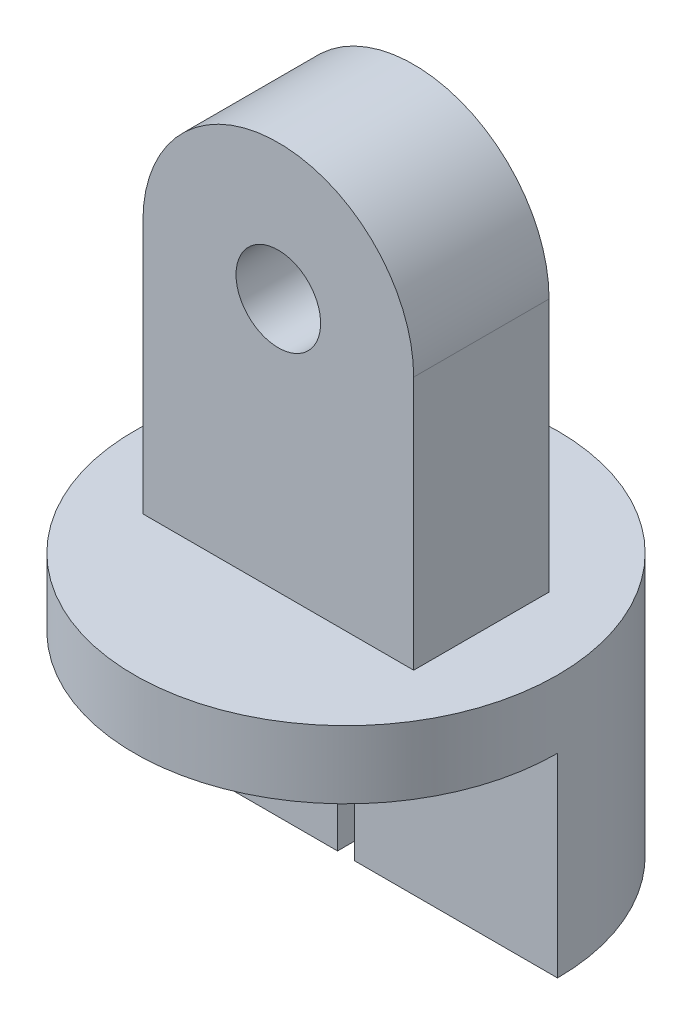
SolidWorks part; units mm, degrees
ref_plane "Front Plane" through (0, 0, 0) normal (0, 0, 1) x (1, 0, 0)
ref_plane "Top Plane" through (0, 0, 0) normal (0, 1, 0) x (1, 0, 0)
ref_plane "Right Plane" through (0, 0, 0) normal (1, 0, 0) x (0, 0, -1)
sketch "Sketch3" plane through (0, 0, 0) normal (0, 0, 1) x (1, 0, 0)
  line L0 (8, 0) -> (-8, 0) construction
  line L1 (8, 0) -> (8, -15)
  line L2 (-8, 0) -> (-8, -15)
  line L3 (8, -15) -> (-8, -15)
  arc A0 (8, 0) -> (-8, 0) centre (0, 0) ccw
  dimension "D1" = 16
  dimension "D2" = 15
extrude "Boss-Extrude2" add sketch "Sketch3" along normal mid plane 8
sketch "Sketch4" plane through (0, 0, -4) normal (0, 0, -1) x (-1, 0, 0)
  circle A0 centre (0, 0) radius 2.5
  dimension "D1" = 5
extrude "Cut-Extrude1" cut sketch "Sketch4" against normal through all
sketch "Sketch6" plane through (0, -15, 0) normal (0, -1, 0) x (1, 0, 0)
  circle A0 centre (0, 0) radius 12.5
  dimension "D1" = 25
extrude "Boss-Extrude3" add sketch "Sketch6" along normal blind 4
sketch "Sketch7" plane through (0, -19, 0) normal (0, -1, 0) x (1, 0, 0)
  line L0 (-12.5, 0) -> (-10.5, 0)
  line L1 (10.5, 0) -> (12.5, 0)
  arc A0 (-12.5, 0) -> (12.5, 0) centre (0, 0) ccw
  arc A1 (-10.5, 0) -> (10.5, 0) centre (0, 0) ccw
  dimension "D1" = 21
  dimension "D2" = 25
extrude "Boss-Extrude4" add sketch "Sketch7" along normal blind 1.5
sketch "Sketch8" plane through (0, -20.5, 0) normal (0, -1, 0) x (1, 0, 0)
  line L0 (-12.5, 0) -> (12.5, 0)
  arc A0 (-12.5, 0) -> (12.5, 0) centre (0, 0) ccw
extrude "Boss-Extrude5" add sketch "Sketch8" along normal blind 10
sketch "Sketch9" plane through (0, -30.5, 0) normal (0, -1, 0) x (1, 0, 0)
  line L0 (12.5, 0) -> (-12.5, 0) construction
  line L1 (-0.5, 0) -> (0.5, 0)
  line L2 (-0.5, 0) -> (-0.5, -7)
  line L3 (-0.5, -7) -> (0.5, -7)
  line L4 (0.5, 0) -> (0.5, -7)
  dimension "D1" = 7
  dimension "D2" = 1
extrude "Cut-Extrude2" cut sketch "Sketch9" against normal up to next
